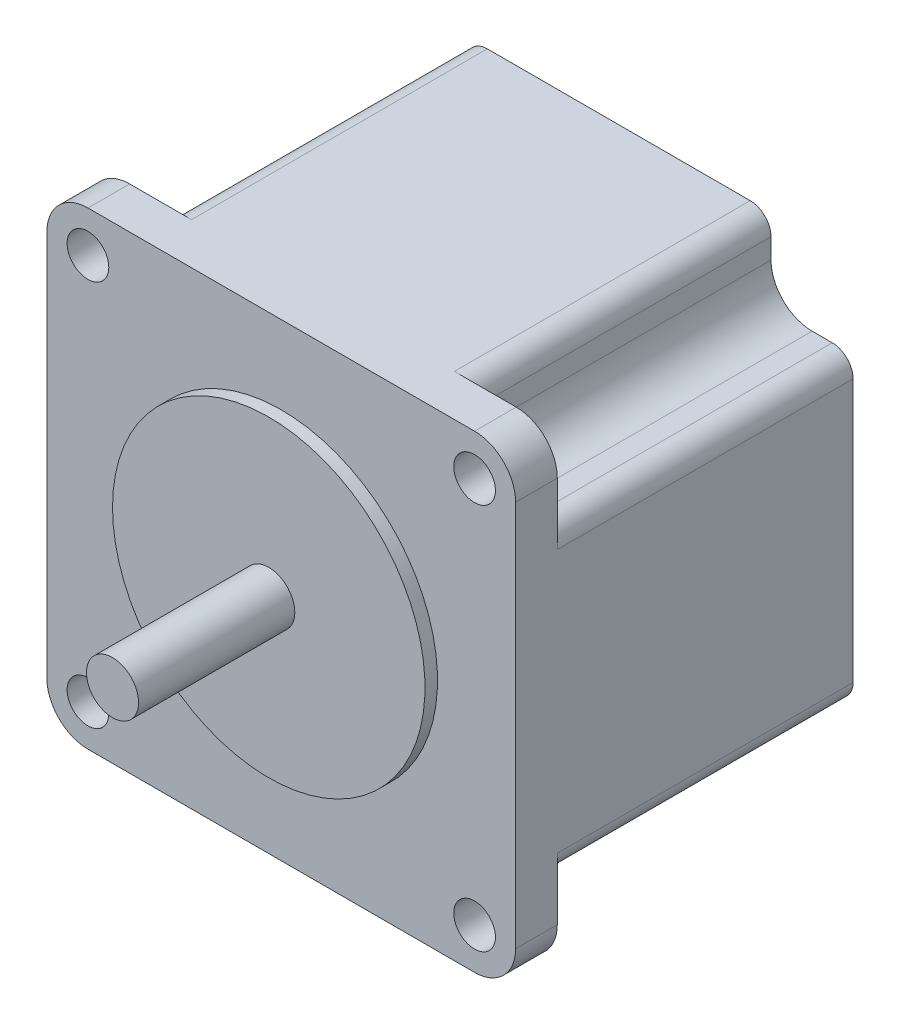
SolidWorks part; units mm, degrees
ref_plane "Front Plane" through (0, 0, 0) normal (0, 0, 1) x (1, 0, 0)
ref_plane "Top Plane" through (0, 0, 0) normal (0, 1, 0) x (1, 0, 0)
ref_plane "Right Plane" through (0, 0, 0) normal (1, 0, 0) x (0, 0, -1)
sketch "Sketch1" plane through (0, 0, 0) normal (0, 0, 1) x (1, 0, 0)
  line L1 (-23.5712, 28.575) -> (23.5712, 28.575)
  line L2 (-28.575, 23.5712) -> (-28.575, -23.5712)
  line L3 (-23.5712, -28.575) -> (23.5712, -28.575)
  line L4 (28.575, 23.5712) -> (28.575, -23.5712)
  line L5 (-28.575, 28.575) -> (28.575, -28.575) construction
  line L6 (-28.575, -28.575) -> (28.575, 28.575) construction
  circle A0 centre (-23.5712, 23.5712) radius 2.54
  circle A1 centre (23.5712, 23.5712) radius 2.54
  circle A2 centre (23.5712, -23.5712) radius 2.54
  circle A3 centre (-23.5712, -23.5712) radius 2.54
  arc A4 (-23.5712, 28.575) -> (-28.575, 23.5712) centre (-23.5712, 23.5712) ccw
  arc A5 (28.575, 23.5712) -> (23.5712, 28.575) centre (23.5712, 23.5712) ccw
  arc A6 (23.5712, -28.575) -> (28.575, -23.5712) centre (23.5712, -23.5712) ccw
  arc A7 (-28.575, -23.5712) -> (-23.5712, -28.575) centre (-23.5712, -23.5712) ccw
  point P0 (0, 0)
  dimension "D5" = 5.08
  dimension "D6" = 5.08
  dimension "D7" = 5.08
  dimension "D8" = 5.08
  dimension "D9" = 5.0038
  dimension "D1" = 57.15
  dimension "D2" = 57.15
  dimension "D3" = 47.1424
  dimension "D4" = 47.1424
extrude "Extrude1" add sketch "Sketch1" against normal mid plane 41.148
sketch "Sketch2" plane through (0, 0, 20.574) normal (0, 0, 1) x (1, 0, 0)
  circle A0 centre (0, 0) radius 19.05
  dimension "D1" = 38.1
extrude "Extrude2" add sketch "Sketch2" along normal blind 1.524
sketch "Sketch3" plane through (0, 0, 20.574) normal (0, 0, 1) x (1, 0, 0)
  circle A0 centre (0, 0) radius 3.175
  dimension "D1" = 6.35
extrude "Extrude3" add sketch "Sketch3" along normal blind 20.574
sketch "Sketch4" plane through (0, 0, -20.574) normal (0, 0, -1) x (-1, 0, 0)
  line L0 (-23.5712, 18.5674) -> (-28.575, 18.5674)
  line L1 (-28.575, -23.5712) -> (-28.575, 23.5712) construction
  line L2 (-28.575, 18.5674) -> (-28.575, 23.5712)
  line L3 (-18.5674, 23.5712) -> (-18.5674, 28.575)
  line L4 (-23.5712, 28.575) -> (23.5712, 28.575) construction
  line L5 (-18.5674, 28.575) -> (-23.5712, 28.575)
  line L6 (23.5712, 18.5674) -> (28.575, 18.5674)
  line L7 (28.575, 23.5712) -> (28.575, -23.5712) construction
  line L8 (28.575, 18.5674) -> (28.575, 23.5712)
  line L9 (18.5674, 23.5712) -> (18.5674, 28.575)
  line L10 (18.5674, 28.575) -> (23.5712, 28.575)
  line L11 (23.5712, -18.5674) -> (28.575, -18.5674)
  line L12 (28.575, -18.5674) -> (28.575, -23.5712)
  line L13 (18.5674, -23.5712) -> (18.5674, -28.575)
  line L14 (23.5712, -28.575) -> (-23.5712, -28.575) construction
  line L15 (18.5674, -28.575) -> (23.5712, -28.575)
  line L16 (-18.5674, -23.5712) -> (-18.5674, -28.575)
  line L17 (-18.5674, -28.575) -> (-23.5712, -28.575)
  line L18 (-23.5712, -18.5674) -> (-28.575, -18.5674)
  line L19 (-28.575, -18.5674) -> (-28.575, -23.5712)
  arc A0 (-23.5712, 18.5674) -> (-18.5674, 23.5712) centre (-23.5712, 23.5712) ccw
  arc A1 (-28.575, -23.5712) -> (-23.5712, -28.575) centre (-23.5712, -23.5712) ccw
  arc A2 (23.5712, -18.5674) -> (18.5674, -23.5712) centre (23.5712, -23.5712) ccw
  arc A3 (18.5674, 23.5712) -> (23.5712, 18.5674) centre (23.5712, 23.5712) ccw
  arc A4 (-23.5712, 28.575) -> (-28.575, 23.5712) centre (-23.5712, 23.5712) ccw
  arc A5 (28.575, 23.5712) -> (23.5712, 28.575) centre (23.5712, 23.5712) ccw
  arc A6 (23.5712, -28.575) -> (28.575, -23.5712) centre (23.5712, -23.5712) ccw
  arc A7 (-18.5674, -23.5712) -> (-23.5712, -18.5674) centre (-23.5712, -23.5712) ccw
extrude "Extrude4" cut sketch "Sketch4" against normal offset from surface (36.068 mm away) 5.08 up to face at (0, 0, 20.574)
fillet "Fillet1" radius 2.54 8 edges at (28.575, -18.5674, -2.54) (18.5674, -28.575, -2.54) (-18.5674, -28.575, -2.54) (-28.575, -18.5674, -2.54) (-28.575, 18.5674, -2.54) (-18.5674, 28.575, -2.54) (18.5674, 28.575, -2.54) (28.575, 18.5674, -2.54)
sketch "Sketch5" plane through (0, 0, -20.574) normal (0, 0, -1) x (-1, 0, 0)
  circle A0 centre (0, 0) radius 3.175
  dimension "D1" = 6.35
extrude "Extrude5" add sketch "Sketch5" along normal blind 14.986
sketch "Sketch6" plane through (0, 0, -20.574) normal (0, 0, -1) x (-1, 0, 0)
  line L0 (-16.0274, 28.575) -> (16.0274, 28.575) construction
  circle A0 centre (-23.0124, 0) radius 1.0782
  circle A1 centre (23.0124, 0) radius 1.0782
  dimension "D1" = 2.1565
  dimension "D2" = 2.1565
  dimension "D3" = 46.0248
  dimension "D4" = 23.0124
  dimension "D5" = 28.575
extrude "Extrude6" cut sketch "Sketch6" against normal blind 3.81
sketch "Sketch7" plane through (0, 0, 22.098) normal (0, 0, 1) x (1, 0, 0)
  circle A0 centre (0, 0) radius 6
  dimension "D1" = 12
ref_axis "shaft" through (0, 0, 22.098) along (0, 0, 1)
